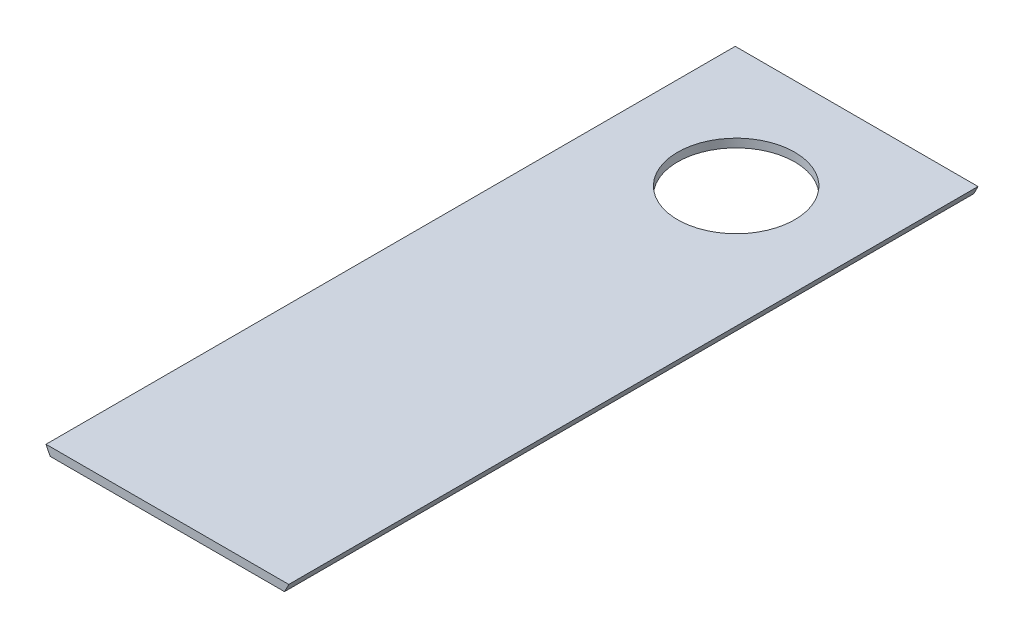
SolidWorks part; units mm, degrees
material "Brass"
ref_plane "Front Plane" through (0, 0, 0) normal (0, 0, 1) x (1, 0, 0)
ref_plane "Top Plane" through (0, 0, 0) normal (0, 1, 0) x (1, 0, 0)
ref_plane "Right Plane" through (0, 0, 0) normal (1, 0, 0) x (0, 0, -1)
sketch "Sketch2" plane through (0, 0, 0) normal (0, 0, 1) x (1, 0, 0)
  line L1 (0, -21.393) -> (0, -24.5934) construction
  line L2 (-44.45, -24.5934) -> (44.45, -24.5934)
  line L4 (-46.0758, -21.393) -> (46.0758, -21.393)
  arc A1 (-46.0758, -21.393) -> (-44.45, -24.5934) centre (0, 0) ccw
  arc A3 (44.45, -24.5934) -> (46.0758, -21.393) centre (0, 0) ccw
  dimension "D2" = 3.2004
extrude "Boss-Extrude1" add sketch "Sketch2" along normal blind 261.62 contours L4 A3 L2 A1
sketch "Sketch3" plane through (0, -24.5934, 0) normal (0, -1, 0) x (1, 0, 0)
  line L0 (-44.45, 45.72) -> (44.45, 45.72) construction
  line L1 (44.45, 261.62) -> (44.45, 0) construction
  line L2 (-44.45, 261.62) -> (-44.45, 0) construction
  line L3 (-44.45, 261.62) -> (44.45, 261.62) construction
  line L4 (0, 45.72) -> (0, 0) construction
  line L5 (-44.45, 0) -> (44.45, 0) construction
  circle A0 centre (0, 45.72) radius 22.225
  dimension "D1" = 44.45
  dimension "D2" = 45.72
extrude "Cut-Extrude1" cut sketch "Sketch3" against normal through all
